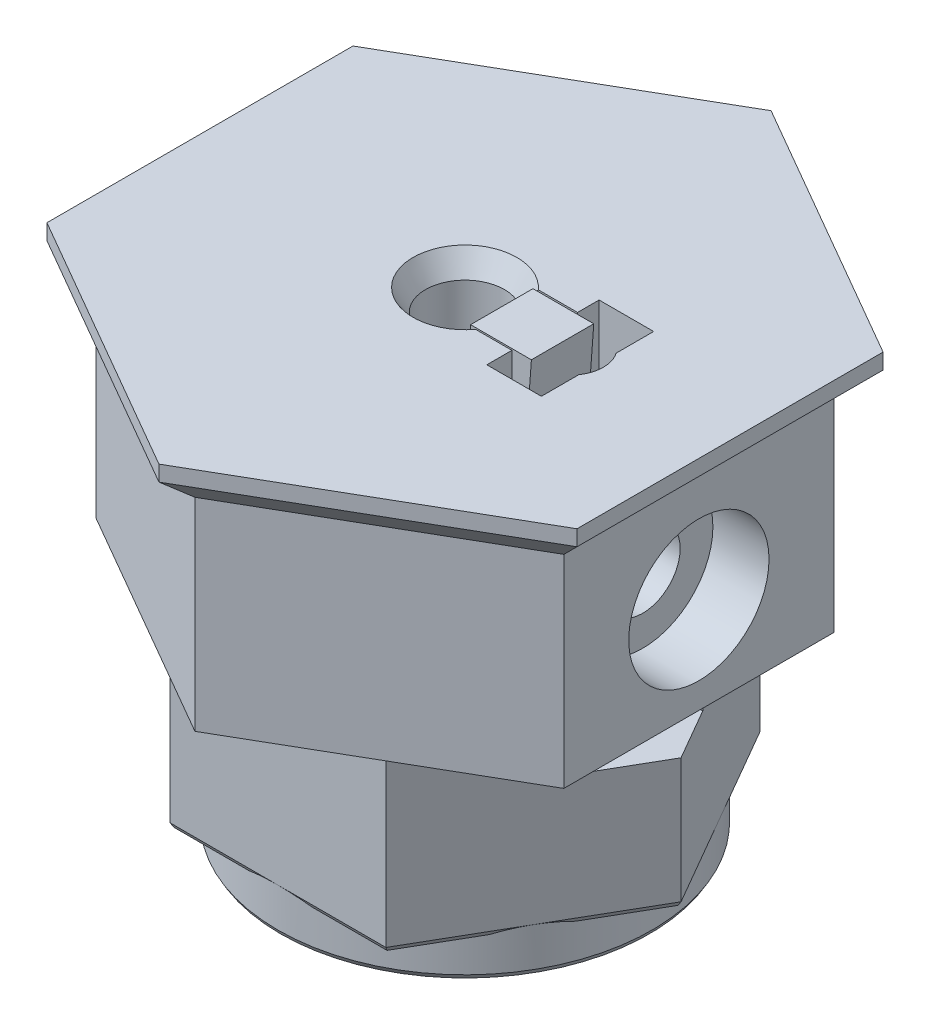
SolidWorks part; units mm, degrees
ref_plane "Ebene vorne" through (0, 0, 0) normal (0, 0, 1) x (1, 0, 0)
ref_plane "Ebene oben" through (0, 0, 0) normal (0, 1, 0) x (1, 0, 0)
ref_plane "Ebene rechts" through (0, 0, 0) normal (1, 0, 0) x (0, 0, -1)
sketch "Skizze1" plane through (0, 0, 0) normal (0, 1, 0) x (1, 0, 0)
  line L1 (15, 8.6603) -> (0, 17.3205)
  line L2 (0, 17.3205) -> (-15, 8.6603)
  line L3 (-15, 8.6603) -> (-15, -8.6603)
  line L4 (-15, -8.6603) -> (0, -17.3205)
  line L5 (0, -17.3205) -> (15, -8.6603)
  line L6 (15, -8.6603) -> (15, 8.6603)
  circle A0 centre (0, 0) radius 15 construction
  circle A1 centre (0, 0) radius 2.53
  dimension "D1" = 5.06
  dimension "D2" = 30
extrude "Aufsatz-Linear austragen1" add sketch "Skizze1" along normal blind 30
sketch "Skizze2" plane through (0, 30, 0) normal (0, 1, 0) x (1, 0, 0)
  line L0 (5, -1.9923) -> (5, -3.6)
  line L1 (5, 3.6) -> (8.5, 3.6)
  line L2 (5, 3.6) -> (5, 2.2173)
  line L3 (5, -3.6) -> (8.5, -3.6)
  line L4 (8.5, 3.6) -> (8.5, -3.6)
  line L5 (5, -1.9923) -> (1.2183, -1.9923)
  line L7 (5, 2.2173) -> (1.2183, 2.2173)
  line L8 (1.2183, -1.9923) -> (1.2183, 2.2173)
  circle A0 centre (0, 0) radius 2.53 construction
  dimension "D1" = 7.2
  dimension "D2" = 3.6
  dimension "D3" = 3.5
  dimension "D4" = 5
extrude "Schnitt-Linear austragen1" cut sketch "Skizze2" against normal blind 18
sketch "Skizze4" plane through (15, 0, 0) normal (1, 0, 0) x (0, 0, -1)
  line L0 (-8.6603, 30) -> (8.6603, 30) construction
  circle A0 centre (0, 20) radius 2.4
  dimension "D1" = 10
extrude "Schnitt-Linear austragen2" cut sketch "Skizze4" against normal blind 16 contours A0
sketch "Skizze6" plane through (0, 30, 0) normal (0, 1, 0) x (1, 0, 0)
  line L1 (0, -19.6299) -> (17, -9.815)
  line L2 (17, -9.815) -> (17, 9.815)
  line L3 (17, 9.815) -> (0, 19.6299)
  line L4 (0, 19.6299) -> (-17, 9.815)
  line L5 (-17, 9.815) -> (-17, -9.815)
  line L6 (-17, -9.815) -> (0, -19.6299)
  circle A1 centre (0, 0) radius 14.009
  circle A2 centre (0, 0) radius 17 construction
extrude "Aufsatz-Linear austragen3" add sketch "Skizze6" against normal blind 3
sketch "Skizze7" plane through (0, 0, 0) normal (0, -1, 0) x (1, 0, 0)
  line L1 (-6.9282, 12) -> (-13.8564, 0)
  line L2 (-13.8564, 0) -> (-6.9282, -12)
  line L3 (-6.9282, -12) -> (6.9282, -12)
  line L4 (6.9282, -12) -> (13.8564, 0)
  line L5 (13.8564, 0) -> (6.9282, 12)
  line L6 (6.9282, 12) -> (-6.9282, 12)
  circle A0 centre (0, 0) radius 12 construction
  circle A1 centre (0, 0) radius 20
extrude "Schnitt-Linear austragen4" cut sketch "Skizze7" against normal blind 14
chamfer "Fase1" distance 0.8 angle 60 1 edges at (-2.5217, 30, 0.2043) first distance on face at (0, 30, 0)
sketch "Skizze9" plane through (10.3923, 0, -6) normal (0.866, 0, -0.5) x (-0.5, 0, -0.866)
  line L0 (6.9282, 14) -> (-6.9282, 14) construction
  line L1 (-3.6, 9) -> (3.5, 9)
  line L2 (-3.6, 9) -> (-3.6, 5.5)
  line L3 (-3.6, 5.5) -> (3.5, 5.5)
  line L4 (3.5, 9) -> (3.5, 5.5)
  dimension "D1" = 7.1
  dimension "D2" = 3.5
  dimension "D3" = 5
extrude "Schnitt-Linear austragen5" cut sketch "Skizze9" against normal blind 16 from offset 8.5 offset against normal yes
sketch "Skizze10" plane through (0, 0, 0) normal (0, -1, 0) x (1, 0, 0)
  circle A0 centre (0, 0) radius 8.5
extrude "Schnitt-Linear austragen6" cut sketch "Skizze10" against normal blind 3
chamfer "Fase2" distance 2 angle 45 6 edges at (8.5, 27, 14.7224) (17, 27, 0) (8.5, 27, -14.7224) (-8.5, 27, -14.7224) (-17, 27, 0) (-8.5, 27, 14.7224)
sketch "Skizze11" plane through (15, 0, 0) normal (1, 0, 0) x (0, 0, -1)
  line L0 (-9.815, 30) -> (9.815, 30) construction
  circle A0 centre (0, 20.1502) radius 4.5
  dimension "D1" = 9
  dimension "D2" = 9.8498
extrude "Schnitt-Linear austragen7" cut sketch "Skizze11" against normal blind 3.6 contours A0
sketch "Skizze12" plane through (0, 0, 0) normal (0, -1, 0) x (1, 0, 0)
  circle A0 centre (0, 0) radius 12
  circle A1 centre (0, 0) radius 14.3384
extrude "Schnitt-Linear austragen8" cut sketch "Skizze12" against normal blind 2.5 contours A0 | A1
chamfer "Fase3" distance 0.3 angle 30 1 edges at (0, 0, -12) first distance on face at (0, 0, -12)
chamfer "Fase4" distance 0.3 angle 30 12 edges at (-8.6603, 2.5, -9) (-8.6603, 2.5, 9) (-12.1244, 2.5, -3) (-12.1244, 2.5, 3) (-3.4641, 2.5, -12) (3.4641, 2.5, -12) (8.6603, 2.5, -9) (12.1244, 2.5, -3) (12.1244, 2.5, 3) (8.6603, 2.5, 9) (3.4641, 2.5, 12) (-3.4641, 2.5, 12) first distance on face at (-10.3923, 7.1, -6) first distance on face at (-10.3673, 7.25, 6.0433) first distance on face at (0, 7.1, -12) first distance on face at (10.3923, 7.1, -6) first distance on face at (10.3923, 7.1, 6) first distance on face at (0, 7.1, 12)
sketch "Skizze13" plane through (0, 12, 0) normal (0, 1, 0) x (1, 0, 0)
  line L0 (1.5593, -1.9923) -> (5, -1.9923) construction
  line L1 (6.15, 2.1077) -> (2.25, 2.1077)
  line L2 (6.15, 2.1077) -> (6.15, -1.8923)
  line L3 (6.15, -1.8923) -> (2.25, -1.8923)
  line L4 (2.25, 2.1077) -> (2.25, -1.8923)
  point P6 (3.2797, -1.9923)
  dimension "D1" = 0.1
  dimension "D2" = 4
  dimension "D3" = 2.25
  dimension "D4" = 3.9
sketch "Skizze14" plane through (0, 12, 0) normal (0, 1, 0) x (1, 0, 0)
  circle A0 centre (6.7754, 0) radius 2.1
extrude "Schnitt-Linear austragen9" cut sketch "Skizze14" against normal blind 21 and the other way blind 18
sketch "Skizze15" plane through (15, 0, 0) normal (1, 0, 0) x (0, 0, -1)
  line L0 (0, 14) -> (-12, 14) construction
  line L1 (-3.9026, 14) -> (3.2974, 14)
  line L2 (-3.9026, 14) -> (-3.9026, 10.8)
  line L3 (-3.9026, 10.8) -> (3.2974, 10.8)
  line L4 (3.2974, 14) -> (3.2974, 10.8)
extrude "Schnitt-Linear austragen12" cut sketch "Skizze15" against normal blind 11 contours L3 L4 L1 L2
sketch "Skizze16" plane through (0, 10.8, 0) normal (0, 1, 0) x (1, 0, 0)
  line L0 (6.15, 2.1077) -> (2.25, 2.1077) construction
  line L1 (1.9406, 2.1077) -> (5.3746, 2.1077)
  line L2 (1.9406, 2.1077) -> (1.9406, -1.9062)
  line L3 (1.9406, -1.9062) -> (5.3746, -1.9062)
  line L4 (5.3746, 2.1077) -> (5.3746, -1.9062)
extrude "Aufsatz-Linear austragen5" add sketch "Skizze13" along normal blind 18 contours L4 L3 L2 L1
chamfer "Fase6" distance 18 angle 4.2 1 edges at (6.15, 12, -0.1077) first distance on face at (6.15, 21, -0.1077)
sketch "Skizze17" plane through (0, 3, 0) normal (0, -1, 0) x (1, 0, 0)
  circle A0 centre (6.7754, 0) radius 4.2
extrude "Schnitt-Linear austragen13" cut sketch "Skizze17" along normal blind 18 and the other way blind 2.2 contours A0
